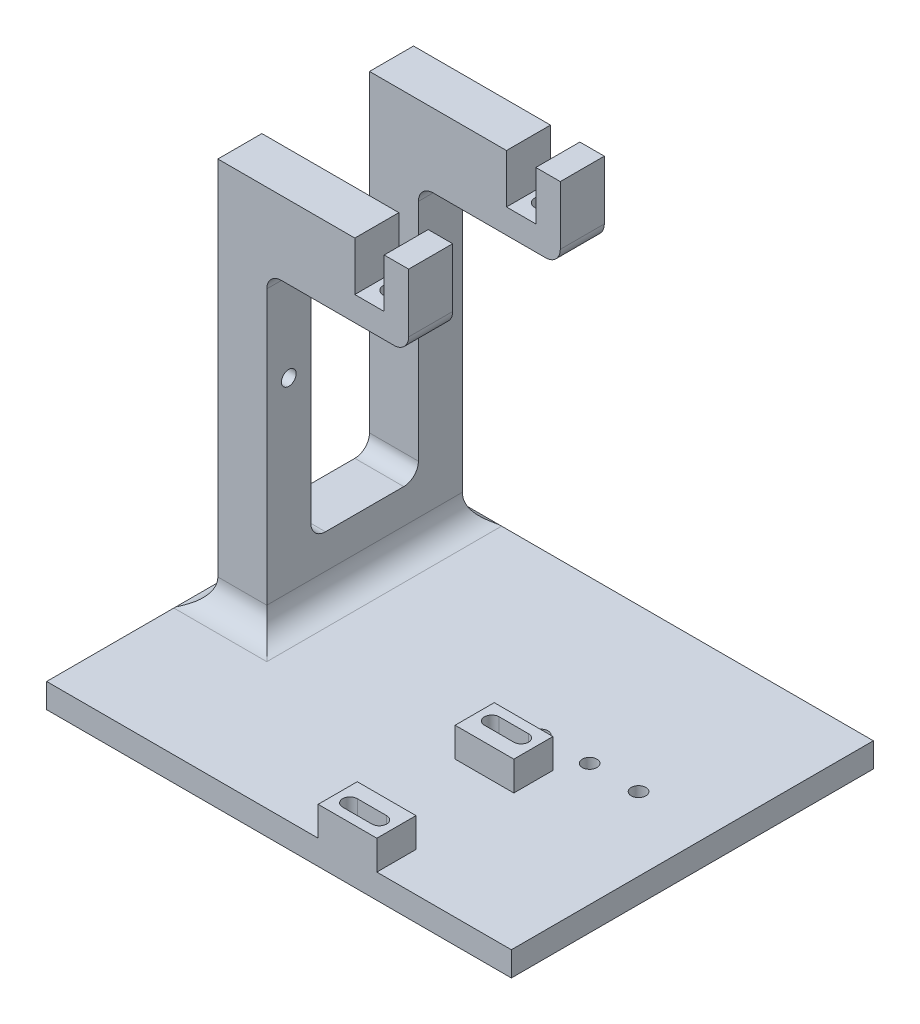
SolidWorks part; units mm, degrees
ref_plane "Front Plane" through (0, 0, 0) normal (0, 0, 1) x (1, 0, 0)
ref_plane "Top Plane" through (0, 0, 0) normal (0, 1, 0) x (1, 0, 0)
ref_plane "Right Plane" through (0, 0, 0) normal (1, 0, 0) x (0, 0, -1)
sketch "Sketch1" plane through (0, 0, 0) normal (0, 0, 1) x (1, 0, 0)
  line L0 (10, 5) -> (45, 5) construction
  line L1 (0, 0) -> (45, 0) construction
  line L2 (0, 0) -> (0, 84) construction
  line L3 (0, 84) -> (28, 84)
  line L5 (10, 5) -> (10, 69)
  line L6 (10, 69) -> (39, 69)
  line L8 (45, 5) -> (45, 0) construction
  line L18 (0, 84) -> (0, 5)
  line L19 (39, 84) -> (39, 69)
  line L20 (28, 84) -> (34, 84) construction
  line L21 (28, 84) -> (34, 84) construction
  line L22 (28, 84) -> (28, 74)
  line L23 (28, 74) -> (34, 74)
  line L24 (34, 84) -> (34, 74)
  line L25 (34, 84) -> (39, 84)
  line L26 (0, 5) -> (10, 5)
  dimension "D2" = 84
  dimension "D3" = 39
  dimension "D4" = 45
  dimension "D5" = 5
  dimension "D6" = 6
  dimension "D7" = 10
  dimension "D1" = 5
  dimension "D8" = 15
  dimension "D9" = 10
extrude "Boss-Extrude1" add sketch "Sketch1" along normal blind 40
sketch "Sketch2" plane through (0, 0, 0) normal (-1, 0, 0) x (0, 0, 1)
  line L1 (9, 84) -> (31, 84)
  line L2 (9, 84) -> (9, 17)
  line L3 (9, 17) -> (31, 17)
  line L4 (31, 84) -> (31, 17)
  line L6 (40, 5) -> (0, 5) construction
  line L7 (40, 84) -> (0, 84) construction
  point P6 (20, 5)
  point P9 (20, 17)
  dimension "D1" = 12
  dimension "D2" = 22
extrude "Cut-Extrude1" cut sketch "Sketch2" against normal through all
sketch "Sketch4" plane through (0, 74, 0) normal (0, 1, 0) x (1, 0, 0)
  line L0 (31, -31) -> (31, -40) construction
  line L1 (34, -31) -> (28, -31) construction
  line L2 (34, -40) -> (28, -40) construction
  line L3 (0, -20) -> (39, -20) construction
  line L6 (0, -9) -> (0, -31) construction
  line L8 (39, -40) -> (39, -31) construction
  circle A0 centre (31, -35.5) radius 1.7
  circle A1 centre (31, -4.5) radius 1.7
  dimension "D1" = 3.4
extrude "Cut-Extrude2" cut sketch "Sketch4" against normal up to next
fillet "Fillet1" radius 3 2 edges at (5, 17, 31) (5, 17, 9)
fillet "Fillet2" radius 3 4 edges at (39, 69, 4.5) (39, 69, 35.5) (10, 69, 35.5) (10, 69, 4.5)
sketch "Sketch10" plane through (10, 0, 0) normal (1, 0, 0) x (0, 0, -1)
  line L1 (-71, 5) -> (3, 5)
  line L2 (-71, 5) -> (-71, 0)
  line L3 (-71, 0) -> (3, 0)
  line L4 (3, 5) -> (3, 0)
  line L5 (0, 5) -> (0, 66) construction
  line L6 (-40, 5) -> (0, 5) construction
  dimension "D1" = 5
  dimension "D2" = 3
  dimension "D3" = 74
extrude "Boss-Extrude2" add sketch "Sketch10" along normal blind 81 and the other way blind 14
sketch "Sketch13" plane through (0, 5, 0) normal (0, 1, 0) x (1, 0, 0)
  line L0 (54.5, -67.5) -> (60.5, -67.5) construction
  line L1 (54.5, -66) -> (60.5, -66)
  line L2 (54.5, -69) -> (60.5, -69)
  line L3 (-4, -71) -> (91, -71) construction
  line L4 (91, 3) -> (91, -71) construction
  line L5 (-4, -56) -> (91, -56) construction
  line L6 (-4, 3) -> (-4, -71) construction
  line L7 (54.5, -38.5) -> (60.5, -38.5) construction
  line L10 (54.5, -37) -> (60.5, -37)
  line L11 (54.5, -40) -> (60.5, -40)
  arc A0 (54.5, -66) -> (54.5, -69) centre (54.5, -67.5) ccw
  arc A1 (60.5, -69) -> (60.5, -66) centre (60.5, -67.5) ccw
  arc A4 (54.5, -37) -> (54.5, -40) centre (54.5, -38.5) ccw
  arc A5 (60.5, -40) -> (60.5, -37) centre (60.5, -38.5) ccw
  point P2 (57.5, -67.5)
  point P19 (57.5, -38.5)
  dimension "D2" = 1.5
  dimension "D1" = 6
  dimension "D3" = 2
  dimension "D4" = 33.5
  dimension "D5" = 15
  dimension "D7" = 29
  dimension "D6" = 2
extrude "Cut-Extrude6" cut sketch "Sketch13" against normal up to next
sketch "Sketch14" plane through (0, 5, 0) normal (0, 1, 0) x (1, 0, 0)
  line L0 (-4, -71) -> (91, -71) construction
  line L1 (51.5, -71) -> (63.5, -71)
  line L2 (51.5, -71) -> (51.5, -63)
  line L3 (51.5, -63) -> (63.5, -63)
  line L4 (63.5, -71) -> (63.5, -63)
  line L6 (54.5, -69) -> (60.5, -69) construction
  line L7 (51.5, -43) -> (51.5, -35)
  line L8 (51.5, -43) -> (63.5, -43)
  line L9 (63.5, -43) -> (63.5, -35)
  line L10 (51.5, -35) -> (63.5, -35)
  line L11 (60.5, -37) -> (54.5, -37) construction
  line L12 (54.5, -40) -> (60.5, -40) construction
  line L13 (60.5, -66) -> (54.5, -66) construction
  line L14 (60.5, -37) -> (54.5, -37)
  line L15 (54.5, -40) -> (60.5, -40)
  line L16 (60.5, -66) -> (54.5, -66)
  line L17 (54.5, -69) -> (60.5, -69)
  arc A0 (54.5, -37) -> (54.5, -40) centre (54.5, -38.5) ccw construction
  arc A1 (60.5, -40) -> (60.5, -37) centre (60.5, -38.5) ccw construction
  arc A2 (54.5, -66) -> (54.5, -69) centre (54.5, -67.5) ccw construction
  arc A3 (60.5, -69) -> (60.5, -66) centre (60.5, -67.5) ccw construction
  arc A4 (54.5, -37) -> (54.5, -40) centre (54.5, -38.5) ccw
  arc A5 (60.5, -40) -> (60.5, -37) centre (60.5, -38.5) ccw
  arc A6 (54.5, -66) -> (54.5, -69) centre (54.5, -67.5) ccw
  arc A7 (60.5, -69) -> (60.5, -66) centre (60.5, -67.5) ccw
  point P6 (57.5, -69)
  point P8 (57.5, -71)
  dimension "D1" = 8
  dimension "D2" = 12
  dimension "D3" = 2
extrude "Boss-Extrude3" add sketch "Sketch14" along normal blind 6
fillet "Fillet3" radius 5 4 edges at (10, 5, 20) (5, 5, 0) (0, 5, 20) (5, 5, 40)
sketch "Sketch15" plane through (0, 5, 0) normal (0, 1, 0) x (1, 0, 0)
  line L0 (91, 3) -> (91, -71) construction
  line L1 (91, -35) -> (51, -35)
  line L2 (91, -35) -> (91, -25)
  line L3 (91, -25) -> (51, -25)
  line L4 (51, -35) -> (51, -25)
  line L5 (15, 3) -> (91, 3) construction
  line L6 (51, -30) -> (91, -30) construction
  line L7 (81, -25) -> (81, -35) construction
  circle A0 centre (56, -30) radius 1.5
  circle A1 centre (66, -30) radius 1.5
  circle A2 centre (76, -30) radius 1.5
  dimension "D5" = 3
  dimension "D6" = 3
  dimension "D7" = 3
  dimension "D1" = 28
  dimension "D2" = 40
  dimension "D3" = 10
  dimension "D4" = 10
  dimension "D8" = 10
  dimension "D9" = 10
  dimension "D10" = 5
extrude "Cut-Extrude8" cut sketch "Sketch15" against normal through all contours A1 | A2 | A0 region at (66, 5, 30) region at (76, 5, 30)
sketch "Sketch16" plane through (10, 0, 0) normal (1, 0, 0) x (0, 0, -1)
  line L0 (-4.5, 66) -> (-4.5, 10) construction
  line L1 (0, 66) -> (-9, 66) construction
  line L2 (-40, 10) -> (0, 10) construction
  line L3 (-20, 17) -> (-20, 84.9261) construction
  line L4 (-12, 17) -> (-28, 17) construction
  circle A0 centre (-4.5, 48) radius 1.5
  circle A1 centre (-35.5, 48) radius 1.5
  point P14 (0, 0)
  point P15 (0, 0)
  point P16 (0, 0)
  dimension "D1" = 3
  dimension "D2" = 38
extrude "Cut-Extrude9" cut sketch "Sketch16" against normal through all
